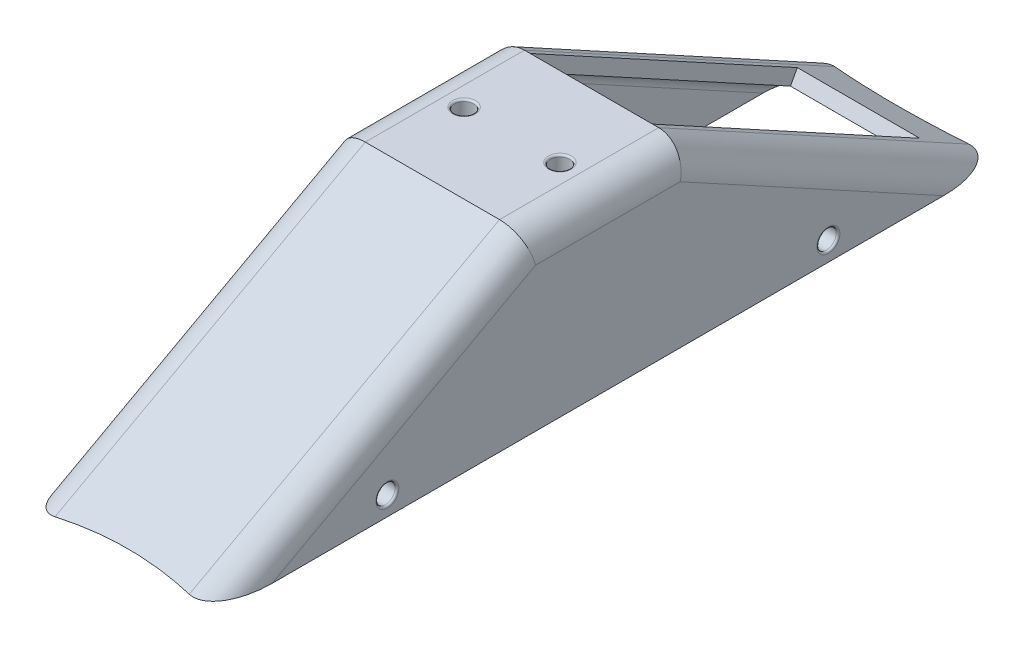
SolidWorks part; units mm, degrees
ref_plane "Front Plane" through (0, 0, 0) normal (0, 0, 1) x (1, 0, 0)
ref_plane "Top Plane" through (0, 0, 0) normal (0, 1, 0) x (1, 0, 0)
ref_plane "Right Plane" through (0, 0, 0) normal (1, 0, 0) x (0, 0, -1)
sketch "Sketch3" plane through (0, 0, 0) normal (0, 0, 1) x (1, 0, 0)
  line L0 (0, 0) -> (0, 8) construction
  line L1 (-10, 8) -> (10, 8)
  line L2 (-10, 8) -> (-10, -10)
  line L4 (10, 8) -> (10, -10)
  arc A0 (-10, -10) -> (10, -10) centre (0, -85.541) cw
  point P0 (0, 0)
  dimension "D3" = 76.2
  dimension "D1" = 20
  dimension "D2" = 18
  dimension "D4" = 8
  dimension "D5" = 18
extrude "Boss-Extrude1" add sketch "Sketch3" along normal blind 82.55
sketch "Sketch4" plane through (-10, 0, 0) normal (-1, 0, 0) x (0, 0, 1)
  line L0 (0, 0) -> (0, -10) construction
  line L1 (0, -10) -> (32.9728, 8)
  line L2 (82.55, 8) -> (0, 8) construction
  line L3 (82.55, -10) -> (0, -10) construction
  line L4 (6.6262, -10) -> (5.1049, -7.2132) construction
  line L5 (6.6262, -10) -> (34.4941, 5.2132) construction
  line L6 (5.1049, -7.2132) -> (32.9728, 8) construction
  line L7 (34.4941, 5.2132) -> (32.9728, 8) construction
  line L8 (0, -10) -> (0, 8)
  line L9 (0, 8) -> (32.9728, 8)
  line L10 (41.275, 8) -> (41.275, -10) construction
  line L11 (82.55, 8) -> (49.5772, 8)
  line L12 (82.55, -10) -> (82.55, 8)
  line L13 (82.55, -10) -> (49.5772, 8)
  dimension "D1" = 3.175
  dimension "D2" = 31.75
extrude "Cut-Extrude1" cut sketch "Sketch4" against normal through all
sketch "Sketch6" plane through (0, -7.7041, 4.2057) normal (0, 0.8777, -0.4792) x (1, 0, 0)
  line L0 (0, 3.4162) -> (0, -32.7745) construction
  line L1 (10, -32.7745) -> (-10, -32.7745) construction
  line L2 (0, -32.7745) -> (6.35, -32.7745) construction
  line L4 (6.35, -32.7745) -> (-6.4117, -32.7745)
  line L5 (6.35, -32.7745) -> (6.35, -1.0245)
  line L6 (6.35, -1.0245) -> (-6.4117, -1.0245)
  line L7 (-6.4117, -32.7745) -> (-6.4117, -1.0245)
  ellipse E0 centre (0, 162.4458) end of major axis (0, 321.4753) minor radius 76.2 (-10, 4.7916) -> (10, 4.7916) ccw construction
  dimension "D1" = 6.35
  dimension "D2" = 31.75
  dimension "D3" = 12.7617
fillet "Fillet3" radius 3 3 edges at (10, -1, 16.4864) (10, 8, 41.275) (10, -1, 66.0636) type face fillet first side face at (10, -1, 41.275) second side face at (0, -0.8352, 16.7882) second side face at (0, 8, 41.275) second side face at (0, -0.8352, 65.7618)
fillet "Fillet4" radius 3 3 edges at (-10, 8, 41.275) (-10, -1, 16.4864) (-10, -1, 66.0636) type face fillet first side face at (-10, -1, 41.275) second side face at (-1.5024, -0.7969, 65.6915) second side face at (-1.5, 8, 41.275) second side face at (-1.5024, -0.7969, 16.8585)
sketch "Sketch7" plane through (0, 8, 0) normal (0, 1, 0) x (1, 0, 0)
  line L0 (-7, -41.275) -> (-5, -41.275) construction
  line L1 (-7, -32.9728) -> (-7, -49.5772) construction
  line L2 (0, -32.9728) -> (0, -49.5772) construction
  line L3 (7, -49.5772) -> (-7, -49.5772) construction
  line L4 (7, -41.275) -> (5, -41.275) construction
  circle A0 centre (-5, -41.275) radius 1
  circle A1 centre (5, -41.275) radius 1
  dimension "D2" = 2
  dimension "D1" = 2
extrude "Cut-Extrude3" cut sketch "Sketch7" against normal blind 2
fillet "Fillet5" radius 0.2 2 edges at (-5, 8, 42.275) (5, 8, 40.275)
extrude "Cut-Extrude4" cut sketch "Sketch6" against normal blind 1.7
sketch "Sketch8" plane through (-10, 0, 0) normal (-1, 0, 0) x (0, 0, 1)
  line L0 (76.289, -10) -> (6.261, -10) construction
  line L1 (41.275, -10) -> (41.275, -8) construction
  line L2 (64.275, -8) -> (18.275, -8) construction
  circle A0 centre (18.275, -8) radius 1
  circle A1 centre (64.275, -8) radius 1
  dimension "D3" = 2
  dimension "D1" = 2
  dimension "D2" = 23
extrude "Cut-Extrude5" cut sketch "Sketch8" against normal blind 2
fillet "Fillet10" radius 0.2 2 edges at (-10, -7, 64.275) (-10, -9, 18.275)
mirror "Mirror3" about plane through (0, 0, 0) normal (1, 0, 0) of "Cut-Extrude5"
fillet "Fillet11" radius 0.2 2 edges at (10, -9, 18.275) (10, -7, 64.275)
shell "Shell10" thickness 1.5 removed face at (9.8, -8, 65.275) removed face at (9.8, -8, 19.275) removed face at (-9.8, -7, 64.275) removed face at (-9.8, -7, 18.275) removed face at (-6.4117, -0.3527, 19.4462) removed face at (6.35, -0.3527, 19.4462) removed face at (-0.0308, -7.9593, 5.5122) removed face at (5, 7.8, 40.275) removed face at (-5, 7.8, 40.275) removed face at (-0.0308, -1.0987, 19.8534) removed face at (0, -9.7482, 41.275) removed face at (-0.0308, 7.2539, 33.3801) removed face at (-8, -7, 64.275) removed face at (-8, -9, 18.275) removed face at (8, -9, 18.275) removed face at (8, -7, 64.275) removed face at (5, 6, 40.275) removed face at (-5, 6, 42.275)
